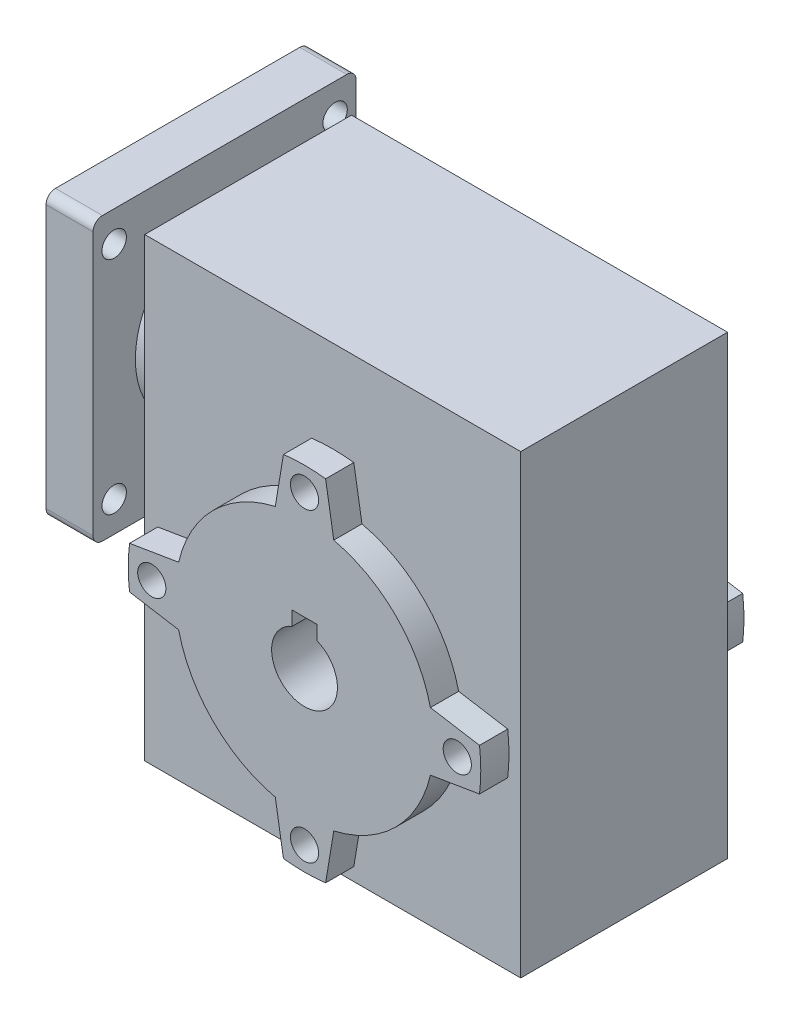
SolidWorks part; units mm, degrees
ref_plane "前视基准面" through (0, 0, 0) normal (0, 0, 1) x (1, 0, 0)
ref_plane "上视基准面" through (0, 0, 0) normal (0, 1, 0) x (1, 0, 0)
ref_plane "右视基准面" through (0, 0, 0) normal (1, 0, 0) x (0, 0, -1)
sketch "草图1" plane through (0, 0, 0) normal (0, 0, 1) x (1, 0, 0)
  line L0 (-29.8155, 43.6532) -> (50.1845, 43.6532)
  line L1 (50.1845, 43.6532) -> (50.1845, -53.3468)
  line L2 (50.1845, -53.3468) -> (-29.8155, -53.3468)
  line L3 (-29.8155, -53.3468) -> (-29.8155, 43.6532)
extrude "凸台-拉伸1" add sketch "草图1" along normal blind 22 and the other way blind 22
sketch "草图2" plane through (0, 0, 22) normal (0, 0, 1) x (1, 0, 0)
  line L0 (10.1845, -53.3468) -> (10.1845, -13.3468) construction
  line L1 (-29.8155, -53.3468) -> (50.1845, -53.3468) construction
  line L2 (5.6967, -50.5772) -> (3.964, -40.134)
  line L3 (14.6724, -50.5772) -> (16.4051, -40.134)
  line L4 (-27.0459, -17.8346) -> (-16.6027, -19.5673)
  line L5 (-27.0459, -8.8589) -> (-16.6027, -7.1262)
  line L6 (5.6967, 23.8837) -> (3.964, 13.4405)
  line L7 (14.6724, 23.8837) -> (16.4051, 13.4405)
  line L8 (47.415, -8.8589) -> (36.9718, -7.1262)
  line L9 (47.415, -17.8346) -> (36.9718, -19.5673)
  arc A0 (-16.6027, -19.5673) -> (3.964, -40.134) centre (10.1845, -13.3468) ccw
  arc A1 (5.6967, -50.5772) -> (14.6724, -50.5772) centre (10.1845, -13.3468) ccw
  circle A2 centre (10.1845, -13.3468) radius 32.5 construction
  circle A3 centre (10.1845, -45.8468) radius 3
  circle A4 centre (-22.3155, -13.3468) radius 3
  circle A5 centre (10.1845, 19.1532) radius 3
  circle A6 centre (42.6845, -13.3468) radius 3
  arc A7 (47.415, -17.8346) -> (47.415, -8.8589) centre (10.1845, -13.3468) ccw
  arc A8 (14.6724, 23.8837) -> (5.6967, 23.8837) centre (10.1845, -13.3468) ccw
  arc A9 (-27.0459, -8.8589) -> (-27.0459, -17.8346) centre (10.1845, -13.3468) ccw
  arc A10 (3.964, 13.4405) -> (-16.6027, -7.1262) centre (10.1845, -13.3468) ccw
  arc A11 (36.9718, -7.1262) -> (16.4051, 13.4405) centre (10.1845, -13.3468) ccw
  arc A12 (16.4051, -40.134) -> (36.9718, -19.5673) centre (10.1845, -13.3468) ccw
  point P34 (10.1845, -13.3468)
  dimension "D1" = 4
extrude "凸台-拉伸2" add sketch "草图2" along normal blind 6
mirror "镜向1" about plane through (0, 0, 0) normal (0, 0, 1) of "凸台-拉伸2"
sketch "草图3" plane through (0, 0, 28) normal (0, 0, 1) x (1, 0, 0)
  line L0 (-9.2609, 6.0987) -> (29.63, -32.7922) construction
  line L1 (10.1845, -13.3468) -> (10.1845, 3.4142) construction
  line L2 (7.5681, -6.8541) -> (7.5681, -3.8541)
  line L3 (7.5681, -3.8541) -> (12.801, -3.8541)
  line L4 (12.801, -3.8541) -> (12.801, -6.8541)
  arc A0 (3.964, 13.4405) -> (-16.6027, -7.1262) centre (10.1845, -13.3468) ccw construction
  arc A1 (16.4051, -40.134) -> (36.9718, -19.5673) centre (10.1845, -13.3468) ccw construction
  arc A2 (7.5681, -6.8541) -> (12.801, -6.8541) centre (10.1845, -13.3468) ccw
  point P14 (8.9351, -6.8541)
  point P18 (8.9351, -6.8541)
extrude "切除-拉伸1" cut sketch "草图3" against normal blind 116
sketch "草图4" plane through (-29.8155, 0, 0) normal (-1, 0, 0) x (0, 0, 1)
  line L0 (-22, -53.3468) -> (-22, -13.3468) construction
  line L2 (-22, -8.8589) -> (-22, -17.8346) construction
  line L3 (-22, -13.3468) -> (22, -13.3468) construction
  line L4 (22, 43.6532) -> (22, -53.3468) construction
  line L5 (0, -13.3468) -> (0, 46.6532) construction
  circle A0 centre (0, 16.6532) radius 19
  circle A1 centre (0, 16.6532) radius 4
  dimension "D1" = 8
extrude "凸台-拉伸3" add sketch "草图4" along normal blind 5
sketch "草图5" plane through (-34.8155, 0, 0) normal (-1, 0, 0) x (0, 0, 1)
  line L0 (0, 35.6532) -> (0, -2.3468) construction
  line L1 (0, 16.6532) -> (0, 46.6532) construction
  line L2 (-26, 46.6532) -> (26, 46.6532)
  line L3 (28, 44.6532) -> (28, -11.3468)
  line L4 (26, -13.3468) -> (-26, -13.3468)
  line L5 (-28, -11.3468) -> (-28, 44.6532)
  line L6 (0, 16.6532) -> (23.5, 16.6532) construction
  line L7 (23.5, 16.6532) -> (23.5, 40.1532) construction
  circle A0 centre (0, 16.6532) radius 19 construction
  circle A1 centre (0, 16.6532) radius 19 construction
  arc A2 (28, 44.6532) -> (26, 46.6532) centre (26, 44.6532) ccw
  arc A3 (26, -13.3468) -> (28, -11.3468) centre (26, -11.3468) ccw
  arc A4 (-26, -13.3468) -> (-28, -11.3468) centre (-26, -11.3468) cw
  arc A5 (-28, 44.6532) -> (-26, 46.6532) centre (-26, 44.6532) cw
  circle A6 centre (23.5, 40.1532) radius 2.6
  circle A7 centre (-23.5, 40.1532) radius 2.6
  circle A8 centre (23.5, -6.8468) radius 2.6
  circle A9 centre (-23.5, -6.8468) radius 2.6
  circle A10 centre (0, 16.6532) radius 4
  point P13 (0, 46.6532)
  dimension "D1" = 2
  dimension "D2" = 8
extrude "凸台-拉伸4" add sketch "草图5" along normal blind 10
sketch "草图6" plane through (-29.8155, 0, 0) normal (-1, 0, 0) x (0, 0, 1)
  circle A0 centre (0, 16.6532) radius 4
extrude "切除-拉伸2" cut sketch "草图6" against normal blind 28
